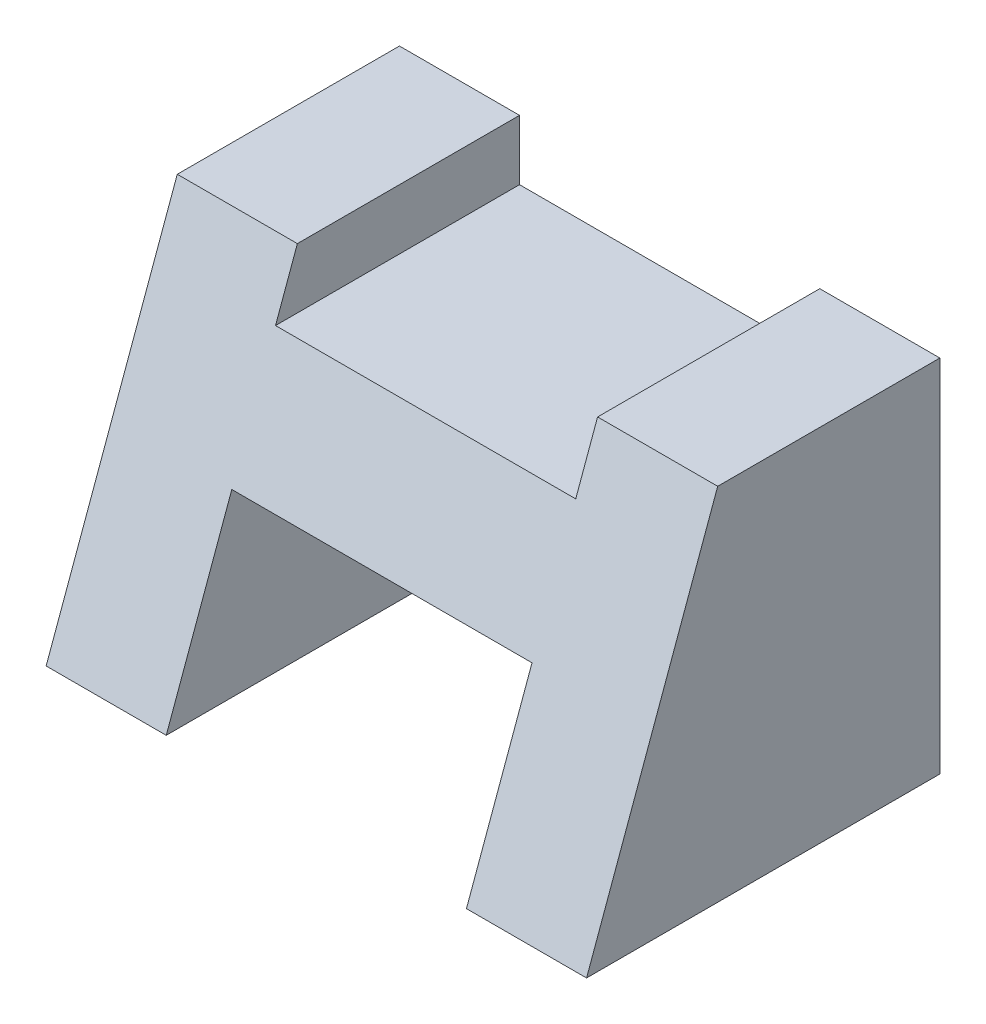
SolidWorks part; units mm, degrees
ref_plane "Płaszczyzna przednia" through (0, 0, 0) normal (0, 0, 1) x (1, 0, 0)
ref_plane "Płaszczyzna górna" through (0, 0, 0) normal (0, 1, 0) x (1, 0, 0)
ref_plane "Płaszczyzna prawa" through (0, 0, 0) normal (1, 0, 0) x (0, 0, -1)
sketch "Szkic1" plane through (0, 0, 0) normal (0, 0, 1) x (1, 0, 0)
  line L1 (0, 0) -> (9, 0)
  line L2 (0, 0) -> (0, 6)
  line L3 (0, 6) -> (9, 6)
  line L4 (9, 0) -> (9, 6)
  line L5 (2, 6) -> (7, 6)
  line L6 (2, 6) -> (2, 0)
  line L7 (2, 0) -> (7, 0)
  line L8 (7, 6) -> (7, 0)
  dimension "D1" = 9
  dimension "D2" = 6
  dimension "D3" = 2
  dimension "D4" = 2
extrude "Dodanie-wyciągnięcie1" add sketch "Szkic1" along normal blind 6 contours L6 L3 L2 L1 | L3 L8 L1 L4 region at (1, 3, 0) region at (8, 3, 0)
sketch "Szkic3" plane through (2, 0, 0) normal (1, 0, 0) x (0, 0, -1)
  line L0 (-6, 6) -> (-6, 0) construction
  line L1 (0, 6) -> (-6, 6)
  line L2 (0, 6) -> (0, 3)
  line L3 (0, 3) -> (-6, 3)
  line L4 (-6, 6) -> (-6, 3)
  dimension "D1" = 3
extrude "Dodanie-wyciągnięcie2" add sketch "Szkic3" along normal blind 5
chamfer "Sfazowanie2" distance 2.3 angle 70 1 edges at (4.5, 6, 6) first distance on face at (4.5, 6, 3)
sketch "Szkic5" plane through (0, 6, 0) normal (0, 1, 0) x (1, 0, 0)
  line L0 (7, -4.7919) -> (2, -4.7919) construction
  line L1 (7, -4.7919) -> (2, -4.7919)
  line L2 (0, 0) -> (9, 0) construction
  line L3 (2, -4.7919) -> (7, -4.7919)
  line L4 (2, -4.7919) -> (2, 0)
  line L5 (2, 0) -> (7, 0)
  line L6 (7, -4.7919) -> (7, 0)
  line M2 (0, -3.7) -> (9, -3.7)
  line M4 (9, 0) -> (0, 0)
extrude "Wytnij-wyciągnięcie1" cut sketch "Szkic5" against normal blind 1 contours L6 L4 M2 M4 | L1 L6 L4 M2 region at (4.5, 6, 4.246) region at (4.5, 6, 1.85)
